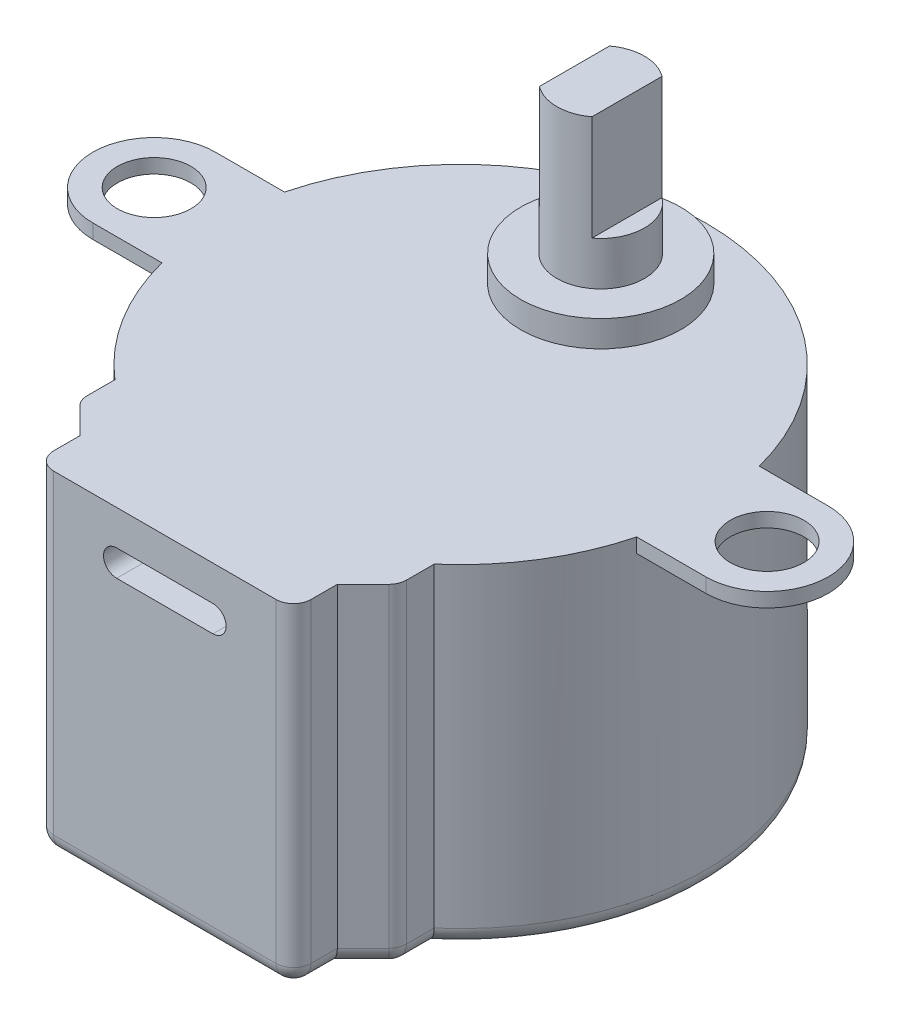
SolidWorks part; units mm, degrees
material "Galvanized Steel"
ref_plane "Front Plane" through (0, 0, 0) normal (0, 0, 1) x (1, 0, 0)
ref_plane "Top Plane" through (0, 0, 0) normal (0, 1, 0) x (1, 0, 0)
ref_plane "Right Plane" through (0, 0, 0) normal (1, 0, 0) x (0, 0, -1)
sketch "Sketch1" plane through (0, 0, 0) normal (0, 1, 0) x (1, 0, 0)
  line L0 (0, 0) -> (0, 60.1731) construction
  circle A0 centre (0, 0) radius 4.57
  dimension "D1" = 9.14
extrude "Boss-Extrude1" add sketch "Sketch1" along normal blind 1.5
sketch "Sketch2" plane through (0, 1.5, 0) normal (0, 1, 0) x (1, 0, 0)
  circle A0 centre (0, 0) radius 2.5
  dimension "D1" = 5
extrude "Boss-Extrude2" add sketch "Sketch2" along normal blind 2.5
sketch "Sketch3" plane through (0, 4, 0) normal (0, 1, 0) x (1, 0, 0)
  line L0 (0, 0) -> (0, 2.5) construction
  line L1 (1.5, 2) -> (1.5, -2)
  line L2 (0, 0) -> (1.5, 0) construction
  line L3 (-1.5, 2) -> (-1.5, -2)
  arc A0 (-1.5, 2) -> (1.5, 2) centre (0, 0) cw
  arc A1 (-1.5, -2) -> (1.5, -2) centre (0, 0) ccw
  dimension "D1" = 2.5
  dimension "D2" = 1.5
extrude "Boss-Extrude3" add sketch "Sketch3" along normal blind 6
sketch "Sketch4" plane through (0, 0, 0) normal (0, 1, 0) x (1, 0, 0)
  line L0 (0, -8) -> (0, 0) construction
  line L1 (0, -8) -> (0, -24.8916) construction
  line L2 (-6.35, -24.8916) -> (6.35, -24.8916)
  line L3 (7.35, -23.8916) -> (7.35, -22.3916)
  line L4 (7.35, -22.3916) -> (8.8249, -20.9167)
  line L5 (9.1178, -20.2096) -> (9.1178, -18.6239)
  line L6 (-9.1178, -20.2096) -> (-9.1178, -18.6239)
  line L7 (-7.35, -22.3916) -> (-8.8249, -20.9167)
  line L8 (-7.35, -23.8916) -> (-7.35, -22.3916)
  arc A0 (8.8249, -20.9167) -> (9.1178, -20.2096) centre (8.1178, -20.2096) ccw
  arc A1 (9.1178, -18.6239) -> (-9.1178, -18.6239) centre (0, -8) ccw
  arc A2 (6.35, -24.8916) -> (7.35, -23.8916) centre (6.35, -23.8916) ccw
  arc A3 (-8.8249, -20.9167) -> (-9.1178, -20.2096) centre (-8.1178, -20.2096) cw
  arc A4 (-6.35, -24.8916) -> (-7.35, -23.8916) centre (-6.35, -23.8916) cw
  point P11 (9.1178, -20.6239)
  point P14 (7.35, -24.8916)
  dimension "D1" = 14
  dimension "D8" = 1
  dimension "D2" = 8
  dimension "D3" = 7.35
  dimension "D4" = 2.5
  dimension "D5" = 45
  dimension "D6" = 2.5
  dimension "D7" = 2
extrude "Boss-Extrude4" add sketch "Sketch4" against normal blind 19
fillet "Fillet1" radius 1 12 edges at (8.0874, -19, 21.6542) (9.0416, -19, 20.5923) (-7.35, -19, 23.1416) (-7.0571, -19, 24.5987) (7.35, -19, 23.1416) (7.0571, -19, 24.5987) (-8.0874, -19, 21.6542) (-9.0416, -19, 20.5923) (9.1178, -19, 19.4167) (0, -19, 24.8916) (-9.1178, -19, 19.4167) (0, -19, -6)
sketch "Sketch5" plane through (0, 0, 0) normal (0, 1, 0) x (1, 0, 0)
  line L0 (13.5554, -4.5) -> (17.5, -4.5)
  line L1 (17.5, -11.5) -> (13.5554, -11.5)
  line L2 (17.5, -8) -> (0, -8) construction
  line L3 (0, -8) -> (0, -24.8916) construction
  line L4 (0, -8) -> (0, 7.3617) construction
  line L5 (-17.5, -11.5) -> (-13.5554, -11.5)
  line L6 (-13.5554, -4.5) -> (-17.5, -4.5)
  arc A0 (17.5, -4.5) -> (17.5, -11.5) centre (17.5, -8) cw
  arc A1 (9.1178, -18.6239) -> (-9.1178, -18.6239) centre (0, -8) ccw construction
  circle A2 centre (17.5, -8) radius 2.1
  arc A3 (13.5554, -4.5) -> (13.5554, -11.5) centre (0, -8) cw
  arc A4 (-13.5554, -4.5) -> (-13.5554, -11.5) centre (0, -8) ccw
  circle A5 centre (-17.5, -8) radius 2.1
  arc A6 (-17.5, -4.5) -> (-17.5, -11.5) centre (-17.5, -8) ccw
  dimension "D1" = 7
  dimension "D3" = 4.2
  dimension "D2" = 17.5
extrude "Boss-Extrude5" add sketch "Sketch5" against normal blind 0.82
sketch "Sketch6" plane through (0, 0, 24.8916) normal (0, 0, 1) x (1, 0, 0)
  line L0 (-2.75, -2) -> (2.75, -2)
  line L1 (2.75, -3.5) -> (-2.75, -3.5)
  line L2 (0, -2) -> (0, 0) construction
  arc A0 (2.75, -2) -> (2.75, -3.5) centre (2.75, -2.75) cw
  arc A1 (-2.75, -3.5) -> (-2.75, -2) centre (-2.75, -2.75) cw
  dimension "D1" = 1.5
  dimension "D2" = 5.5
  dimension "D3" = 2
extrude "Cut-Extrude1" cut sketch "Sketch6" against normal blind 2
